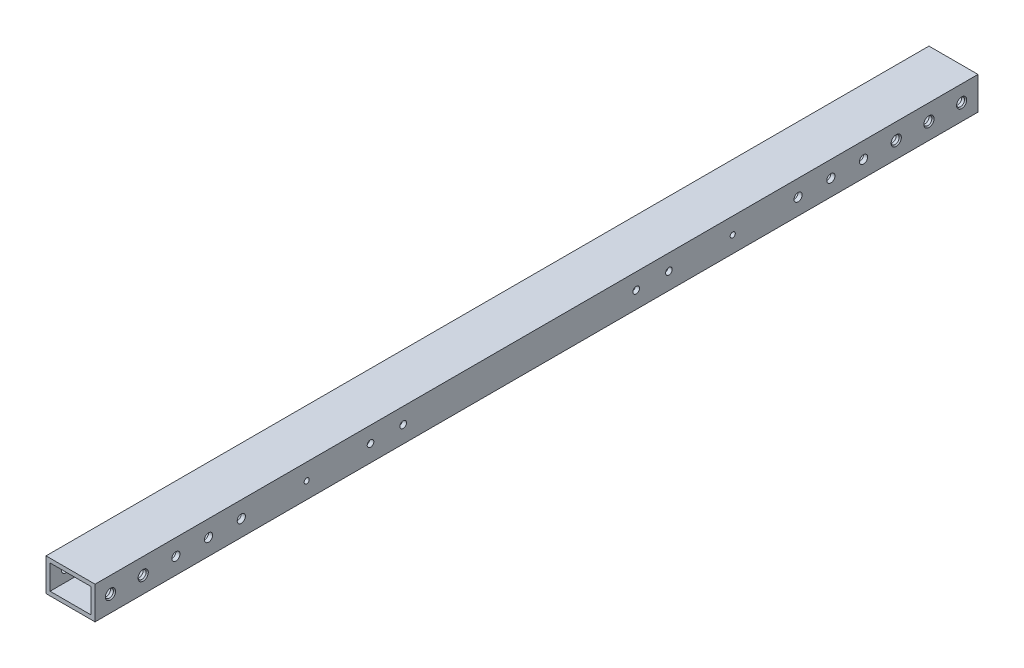
SolidWorks part; units mm, degrees
ref_plane "Front Plane" through (0, 0, 0) normal (0, 0, 1) x (1, 0, 0)
ref_plane "Top Plane" through (0, 0, 0) normal (0, 1, 0) x (1, 0, 0)
ref_plane "Right Plane" through (0, 0, 0) normal (1, 0, 0) x (0, 0, -1)
sketch "Sketch1" plane through (0, 0, 0) normal (0, 0, 1) x (1, 0, 0)
  line L0 (-15.875, 9.525) -> (15.875, 9.525)
  line L2 (-19.05, 12.7) -> (19.05, 12.7)
  line L3 (-19.05, 12.7) -> (-19.05, -12.7)
  line L4 (-19.05, -12.7) -> (19.05, -12.7)
  line L5 (19.05, 12.7) -> (19.05, -12.7)
  line L10 (15.875, 9.525) -> (15.875, -9.525)
  line L11 (-15.875, -9.525) -> (15.875, -9.525)
  line L12 (-15.875, 9.525) -> (-15.875, -9.525)
  point P12 (0, 12.7)
  point P14 (19.05, 0)
  dimension "Wall Thickness" = 3.175
  dimension "Outside Width" = 38.1
  dimension "Outside Height" = 25.4
  dimension "Inside Height" = 19.05
  dimension "Inside Width" = 31.75
sketch "Sketch2" plane through (0, 0, 0) normal (1, 0, 0) x (0, 0, -1)
  line L0 (342.9, 0) -> (-342.9, 0)
  point P4 (0, 0)
  point P7 (-342.9, 0)
  point P10 (342.9, 0)
  dimension "Length" = 685.8
sketch "Sketch3" plane through (0, 0, 0) normal (0, 0, 1) x (1, 0, 0)
  line L21 (19.05, 12.7) -> (-19.05, 12.7)
  line L22 (19.05, -12.7) -> (19.05, 12.7)
  line L23 (-19.05, -12.7) -> (19.05, -12.7)
  line L24 (-19.05, 12.7) -> (-19.05, -12.7)
  line L25 (19.05, 12.7) -> (-19.05, 12.7)
  line L26 (19.05, -12.7) -> (19.05, 12.7)
  line L27 (-19.05, -12.7) -> (19.05, -12.7)
  line L28 (-19.05, 12.7) -> (-19.05, -12.7)
  line L29 (15.875, 9.525) -> (-15.875, 9.525)
  line L30 (15.875, -9.525) -> (15.875, 9.525)
  line L31 (-15.875, -9.525) -> (15.875, -9.525)
  line L32 (-15.875, 9.525) -> (-15.875, -9.525)
  line L33 (15.875, 9.525) -> (-15.875, 9.525)
  line L34 (15.875, -9.525) -> (15.875, 9.525)
  line L35 (-15.875, -9.525) -> (15.875, -9.525)
  line L36 (-15.875, 9.525) -> (-15.875, -9.525)
  dimension "D1" = 0
  dimension "D2" = 0
extrude "Boss-Extrude1" add sketch "Sketch3" along normal up to vertex (342.9 mm away) and the other way up to vertex (342.9 mm away) up to point (0, 0, 342.9) other way up to point (0, 0, -342.9)
sketch "Drawing Reference" plane through (0, 0, 0) normal (1, 0, 0) x (0, 0, -1)
  line L0 (-342.9, 0) -> (342.9, 0) construction
  line L1 (0, -12.7) -> (0, 12.7) construction
  line L2 (-342.9, -12.7) -> (342.9, -12.7) construction
  line L5 (-342.9, 12.7) -> (342.9, 12.7) construction
  point P7 (-315.468, 0)
  point P8 (315.468, 0)
  dimension "D1" = 27.432
sketch "Sketch4" plane through (-19.05, 0, 0) normal (-1, 0, 0) x (0, 0, 1)
  line L0 (-342.9, 0) -> (-330.2, 0)
  line L1 (-342.9, 12.7) -> (-342.9, -12.7) construction
  line L2 (-330.2, 0) -> (-304.8, 0)
  line L3 (-304.8, 0) -> (-279.4, 0)
  line L4 (-279.4, 0) -> (-254, 0)
  line L5 (-254, 0) -> (-228.6, 0)
  line L6 (-228.6, 0) -> (-203.2, 0)
  line L7 (342.9, 0) -> (330.9118, 0)
  line L8 (342.9, 12.7) -> (342.9, -12.7) construction
  line L9 (330.9118, 0) -> (305.5118, 0)
  line L10 (305.5118, 0) -> (280.1118, 0)
  line L11 (280.1118, 0) -> (254.7118, 0)
  line L12 (254.7118, 0) -> (229.3118, 0)
hole_wizard "1/4 (0.25) Diameter Hole2" positions "Sketch7" profile "Sketch8" hole size "1/4" standard "ANSI Inch" end condition through all
sketch "Sketch7" plane through (-19.05, 0, 0) normal (-1, 0, 0) x (0, 0, 1)
  point P0 (-330.2, 0)
  point P3 (-304.8, 0)
  point P7 (330.9118, 0)
  point P11 (-279.4, 0)
  point P14 (305.5118, 0)
sketch "Sketch8" plane through (-19.05, 0, -330.2) normal (0, 1, 0) x (0, 0, 1)
  line L0 (0, 0) -> (0, 38.1)
  line L1 (0, 38.1) -> (3.9624, 38.1)
  line L2 (3.175, 37.1942) -> (3.175, 0)
  line L5 (3.175, 0) -> (0, 0)
  line L7 (3.9624, 38.1) -> (3.175, 37.1942)
  line L8 (-3.9624, 38.1) -> (-3.175, 37.1942) construction
  line L11 (0, -6.35) -> (0, 107.95) construction
  dimension "Thru Hole Dia." = 6.35
  dimension "Thru Hole Depth" = 38.1
  dimension "Far C'Sink Dia." = 7.9248
  dimension "Far C'Sink Angle" = 82
hole_wizard "1/4 (0.25) Diameter Hole3" positions "Sketch9" profile "Sketch10" hole size "1/4" standard "ANSI Inch" end condition through all
sketch "Sketch9" plane through (19.05, 0, 0) normal (1, 0, 0) x (0, 0, -1)
  point P0 (-280.1118, 0)
  point P3 (-254.7118, 0)
  point P6 (-229.3118, 0)
  point P9 (254, 0)
  point P12 (228.6, 0)
  point P15 (203.2, 0)
sketch "Sketch10" plane through (19.05, 0, 280.1118) normal (0, 1, 0) x (0, 0, -1)
  line L0 (0, 0) -> (0, 38.1)
  line L1 (0, 38.1) -> (3.175, 38.1)
  line L2 (3.175, 38.1) -> (3.175, 0)
  line L5 (3.175, 0) -> (0, 0)
  line L11 (0, -6.35) -> (0, 107.95) construction
  dimension "Thru Hole Dia." = 6.35
  dimension "Thru Hole Depth" = 38.1
hole_wizard "5/32 (0.15625) Diameter Hole1" positions "Sketch11" profile "Sketch12" hole size "5/32" standard "ANSI Inch" end condition through all
sketch "Sketch11" plane through (19.05, 0, 0) normal (1, 0, 0) x (0, 0, -1)
  point P0 (152.4, 0)
  point P3 (-178.5118, 0)
sketch "Sketch12" plane through (19.05, 0, -152.4) normal (0, 1, 0) x (0, 0, -1)
  line L0 (0, 0) -> (0, 38.1)
  line L1 (0, 38.1) -> (1.9844, 38.1)
  line L2 (1.9844, 38.1) -> (1.9844, 0)
  line L5 (1.9844, 0) -> (0, 0)
  line L11 (0, -6.35) -> (0, 107.95) construction
  dimension "Thru Hole Dia." = 3.9688
  dimension "Thru Hole Depth" = 38.1
sketch "Sketch13" plane through (19.05, 0, 0) normal (1, 0, 0) x (0, 0, -1)
  line L0 (-103.5434, 0.3445) -> (-128.9434, 0.3445)
  line L1 (77.4316, 0.355) -> (102.8316, 0.355)
  point P8 (77.4316, 0.355)
hole_wizard "#10 Clearance Hole1" positions "Sketch14" profile "Sketch15" hole size "#10" standard "ANSI Inch" end condition through all
sketch "Sketch14" plane through (19.05, 0, 0) normal (1, 0, 0) x (0, 0, -1)
  point P0 (-128.9434, 0.3445)
  point P3 (-103.5434, 0.3445)
  point P7 (77.4316, 0.355)
  point P10 (102.8316, 0.355)
sketch "Sketch15" plane through (19.05, 0.3445, 128.9434) normal (0, 1, 0) x (0, 0, -1)
  line L0 (0, 0) -> (0, 38.1)
  line L1 (0, 38.1) -> (2.5527, 38.1)
  line L2 (2.5527, 38.1) -> (2.5527, 0)
  line L5 (2.5527, 0) -> (0, 0)
  line L11 (0, -6.35) -> (0, 107.95) construction
  dimension "Thru Hole Dia." = 5.1054
  dimension "Thru Hole Depth" = 38.1
equation "\"D1@Drawing Reference\"=\"Outside Width@Sketch1\" * 0.72"
